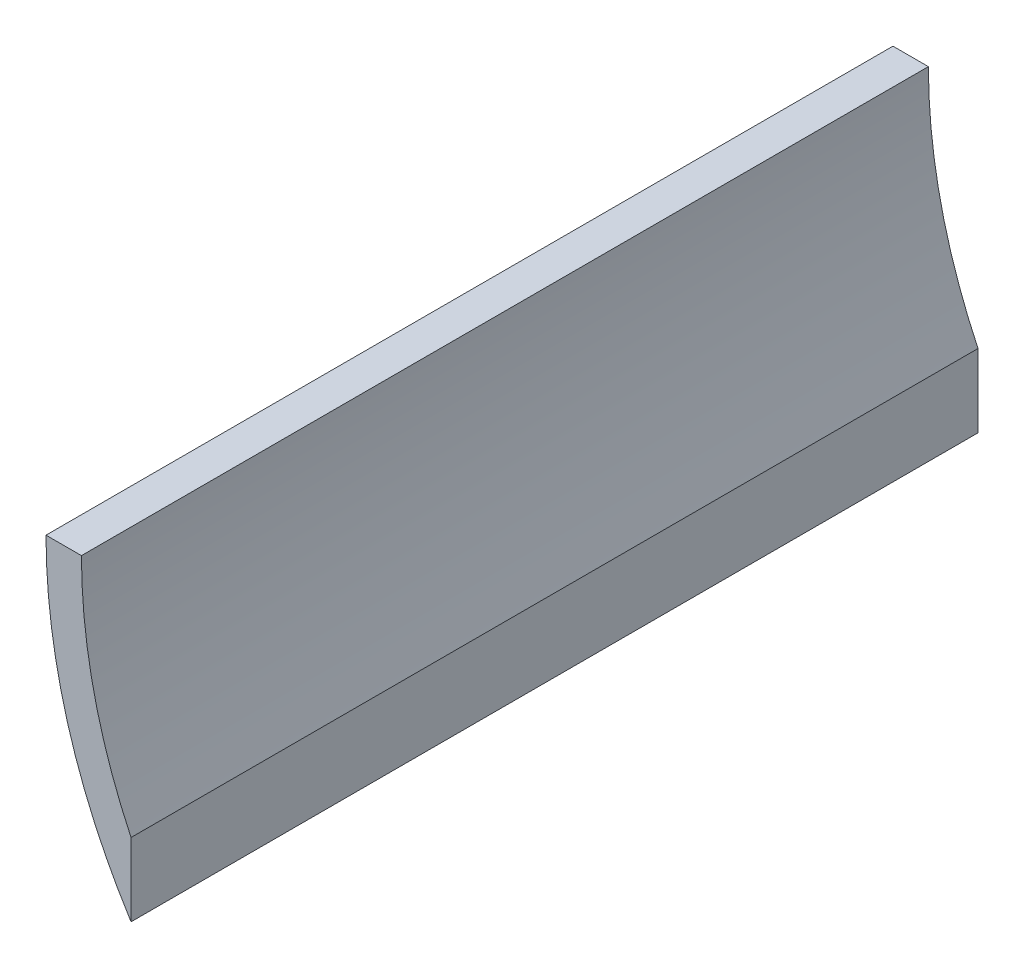
SolidWorks part; units mm, degrees
material "that blue high density foam"
ref_plane "Front" through (0, 0, 0) normal (0, 0, 1) x (1, 0, 0)
ref_plane "Top" through (0, 0, 0) normal (0, 1, 0) x (1, 0, 0)
ref_plane "Right" through (0, 0, 0) normal (1, 0, 0) x (0, 0, -1)
sketch "Sketch1" plane through (0, 0, 0) normal (0, 0, 1) x (1, 0, 0)
  line L2 (-82, -47.1761) -> (-82, -67.7866)
  line L3 (-96, 14.7134) -> (-106, 14.7134)
  line L5 (-82, -67.7866) -> (-82, -25.6187) construction
  line L6 (-96, 35.7134) -> (-96, 14.7134) construction
  arc A0 (-106, 14.7134) -> (-82, -67.7866) centre (47.7969, 14.7134) ccw construction
  arc A1 (-106, 14.7134) -> (-82, -67.7866) centre (47.7969, 14.7134) ccw
  arc A2 (-96, 14.7134) -> (-82, -47.1761) centre (47.7969, 14.7134) ccw
  point P0 (-96, 14.7134)
  dimension "D1" = 10
extrude "Boss-Extrude1" add sketch "Sketch1" along normal up to surface (239 mm away)
